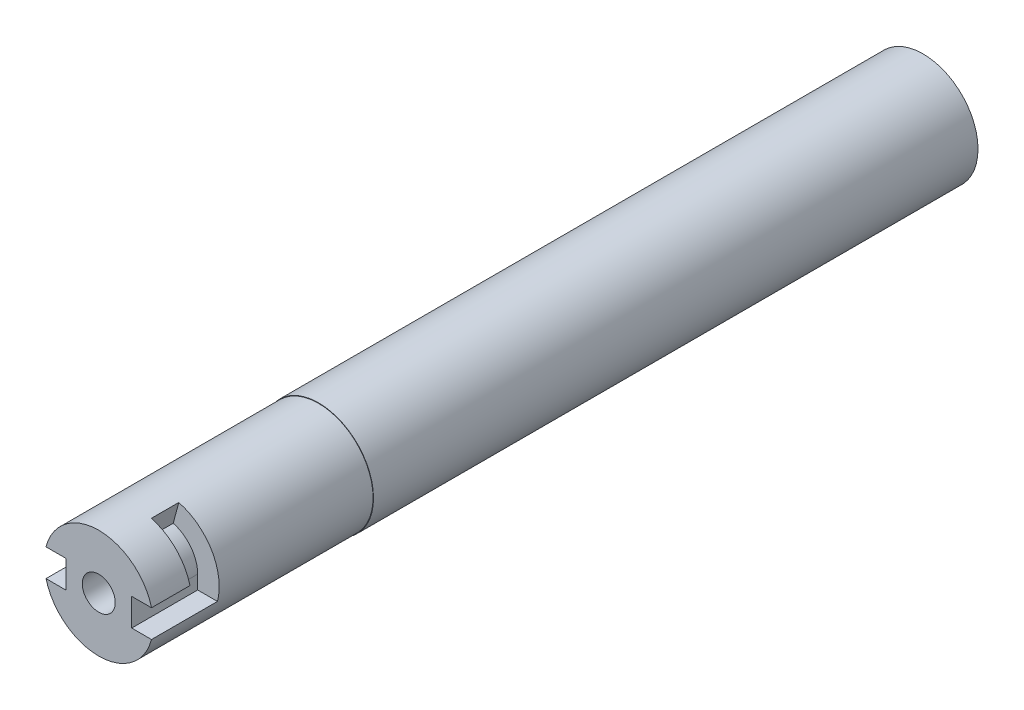
SolidWorks part; units mm, degrees
ref_plane "Front Plane" through (0, 0, 0) normal (0, 0, 1) x (1, 0, 0)
ref_plane "Top Plane" through (0, 0, 0) normal (0, 1, 0) x (1, 0, 0)
ref_plane "Right Plane" through (0, 0, 0) normal (1, 0, 0) x (0, 0, -1)
sketch "Sketch1" plane through (0, 0, 0) normal (0, 0, 1) x (1, 0, 0)
  circle A0 centre (0, 0) radius 6.35
  dimension "D1" = 12.7
extrude "Boss-Extrude1" add sketch "Sketch1" along normal blind 95.25
sketch "Sketch2" plane through (0, 0, 0) normal (0, 0, -1) x (-1, 0, 0)
  circle A0 centre (0, 0) radius 5.08
  dimension "D1" = 10.16
extrude "Cut-Extrude1" cut sketch "Sketch2" against normal offset from surface (82.55 mm away) 12.7 up to face at (6.35, 0, 95.25)
sketch "Sketch3" plane through (0, 0, 95.25) normal (0, 0, 1) x (1, 0, 0)
  circle A0 centre (0, 0) radius 1.905
  dimension "D1" = 3.81
extrude "Cut-Extrude2" cut sketch "Sketch3" against normal blind 114.3
sketch "Sketch5" plane through (0, 0, 95.25) normal (0, 0, 1) x (1, 0, 0)
  line L0 (6.1484, 1.5875) -> (3.81, 1.5875)
  line L1 (3.81, 1.5875) -> (3.81, -1.5875)
  line L2 (3.81, -1.5875) -> (6.1484, -1.5875)
  line L3 (0, 0) -> (6.35, 0) construction
  line L4 (0, 0) -> (0, -6.35) construction
  line L5 (-6.1484, 1.5875) -> (-3.81, 1.5875)
  line L6 (-3.81, -1.5875) -> (-6.1484, -1.5875)
  line L7 (-3.81, 1.5875) -> (-3.81, -1.5875)
  circle A1 centre (0, 0) radius 6.35
  circle A2 centre (0, 0) radius 6.35
  point P5 (3.81, 0)
  circle M8 centre (0, 0) radius 6.35
  dimension "D2" = 3.175
  dimension "D3" = 2.54
  dimension "D1" = 0
extrude "Cut-Extrude8" cut sketch "Sketch5" against normal blind 7.62 contours L1 L2 L0 M8 | L7 L5 L6 M8 region at (5.0473, 0, 95.25) region at (-5.0473, 0, 95.25)
sketch "Sketch6" plane through (0, 0, 95.25) normal (0, 0, 1) x (1, 0, 0)
  circle A0 centre (0, 0) radius 6.35
sketch "Sketch7" plane through (0, 0, 0) normal (0, 1, 0) x (1, 0, 0)
  line L1 (0, 0) -> (0, -95.25) construction
  line L2 (6.1484, -87.63) -> (3.81, -87.63) construction
  line L3 (6.1484, -87.63) -> (3.81, -87.63)
  line L4 (6.35, -90.805) -> (6.35, -87.63)
  line L5 (6.35, -87.63) -> (6.1484, -87.63)
  line L6 (3.81, -87.63) -> (3.81, -90.805)
  line L7 (3.81, -90.805) -> (6.35, -90.805)
  line L8 (-6.35, -95.25) -> (6.35, -95.25) construction
  line L9 (-3.81, -90.805) -> (-6.35, -90.805)
  line L10 (-3.81, -87.63) -> (-3.81, -90.805)
  line L11 (-6.35, -87.63) -> (-6.1484, -87.63)
  line L12 (-6.35, -90.805) -> (-6.35, -87.63)
  line L13 (-6.1484, -87.63) -> (-3.81, -87.63)
  dimension "D1" = 3.175
ref_axis "Axis1" through (0, 0, 95.25) along (0, 0, -1)
revolve "Cut-Revolve1" cut sketch "Sketch7" angle 75 about L1
sketch "Sketch8" plane through (0, 0, 95.25) normal (0, 0, 1) x (1, 0, 0)
  circle A0 centre (0, 0) radius 6.2992
  circle A1 centre (0, 0) radius 6.35 construction
  circle A2 centre (0, 0) radius 6.35
  dimension "D1" = 12.5984
extrude "Cut-Extrude10" cut sketch "Sketch8" against normal blind 25.4
